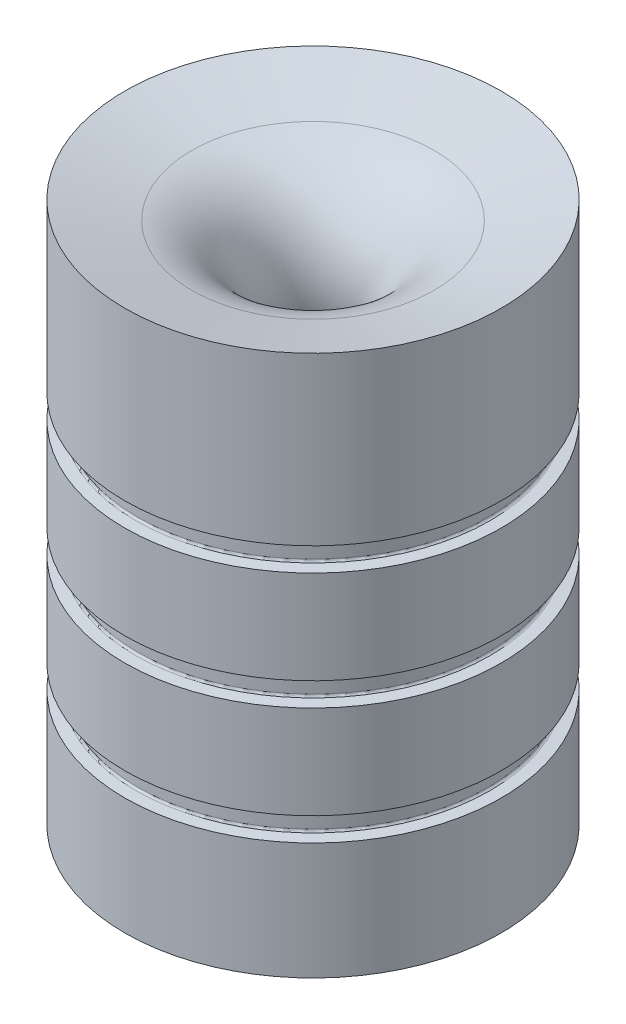
SolidWorks part; units mm, degrees
material "C (Graphite)"
ref_plane "Front Plane" through (0, 0, 0) normal (0, 0, 1) x (1, 0, 0)
ref_plane "Top Plane" through (0, 0, 0) normal (0, 1, 0) x (1, 0, 0)
ref_plane "Right Plane" through (0, 0, 0) normal (1, 0, 0) x (0, 0, -1)
sketch "Sketch1" plane through (0, 0, 0) normal (0, 0, 1) x (1, 0, 0)
  line L0 (0, -55) -> (0, 55) construction
  line L1 (41.275, 118.6571) -> (41.275, 0)
  line L2 (41.275, 118.6571) -> (26.581, 114.7199)
  line L3 (41.275, 0) -> (34.544, 0)
  line L4 (34.544, 0) -> (11.0246, 87.7755)
  line L5 (0, 11.2039) -> (0, 47.7588) construction
  arc A0 (11.0246, 87.7755) -> (26.581, 114.7199) centre (32.275, 93.4695) cw
  dimension "D6" = 32.275
  dimension "D3" = 22
  dimension "D1" = 41.275
  dimension "D2" = 34.544
  dimension "D4" = 105
  dimension "D5" = 75
revolve "Revolve1" add sketch "Sketch1" angle 360 about L5
ref_plane "Plane1" through (0, 11.2039, 0) normal (-1, 0, 0) x (0, 0, -1)
sketch "Sketch3" plane through (0, 11.2039, 0) normal (-1, 0, 0) x (0, 0, -1)
  line L0 (38.8614, -14.6501) -> (41.3639, -14.4311)
  line L1 (41.3639, -14.4311) -> (41.3639, -19.6188)
  line L2 (41.3639, -19.6188) -> (38.8614, -19.3999)
  line L3 (38.4556, -18.957) -> (38.4556, -15.0929)
  line L4 (0, 50) -> (0, -50) construction
  line L5 (41.275, 11.2039) -> (-41.275, 11.2039) construction
  arc A0 (38.8614, -19.3999) -> (38.4556, -18.957) centre (38.9001, -18.957) cw
  arc A1 (38.4556, -15.0929) -> (38.8614, -14.6501) centre (38.9001, -15.0929) cw
  dimension "D1" = 25.635
revolve "Groove for AS 568-234, O-Ring1" cut sketch "Sketch3"
pattern_linear "LPattern1" count 3 spacing 25.635 along (0, 1, 0) of "Groove for AS 568-234, O-Ring1"
